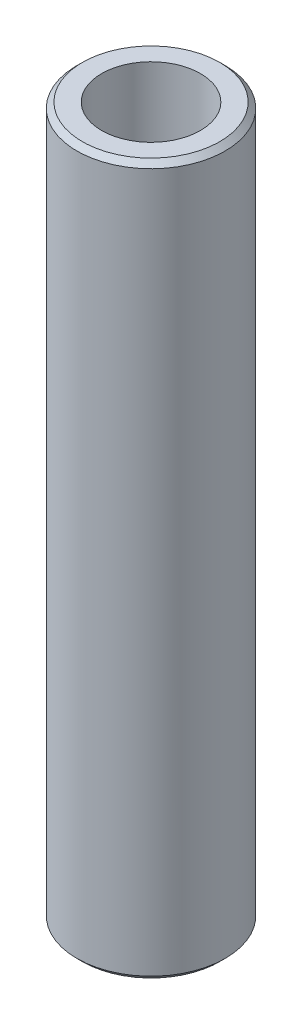
SolidWorks part; units mm, degrees
ref_plane "Front Plane" through (0, 0, 0) normal (0, 0, 1) x (1, 0, 0)
ref_plane "Top Plane" through (0, 0, 0) normal (0, 1, 0) x (1, 0, 0)
ref_plane "Right Plane" through (0, 0, 0) normal (1, 0, 0) x (0, 0, -1)
sketch "Sketch1" plane through (0, 0, 0) normal (0, 1, 0) x (1, 0, 0)
  circle A0 centre (0, 0) radius 40
  dimension "SHAFT_OD" = 80
extrude "Boss-Extrude1" add sketch "Sketch1" along normal blind 383.3203
sketch "Sketch2" plane through (0, 0, 0) normal (0, 1, 0) x (1, 0, 0)
  circle A0 centre (0, 0) radius 26.6566
  dimension "BORE_D" = 53.3133
extrude "Cut-Extrude1" cut sketch "Sketch2" along normal through all
chamfer "Chamfer1" distance 2.9172 angle 45 2 edges at (0, 383.3203, 40) (0, 0, 40)
